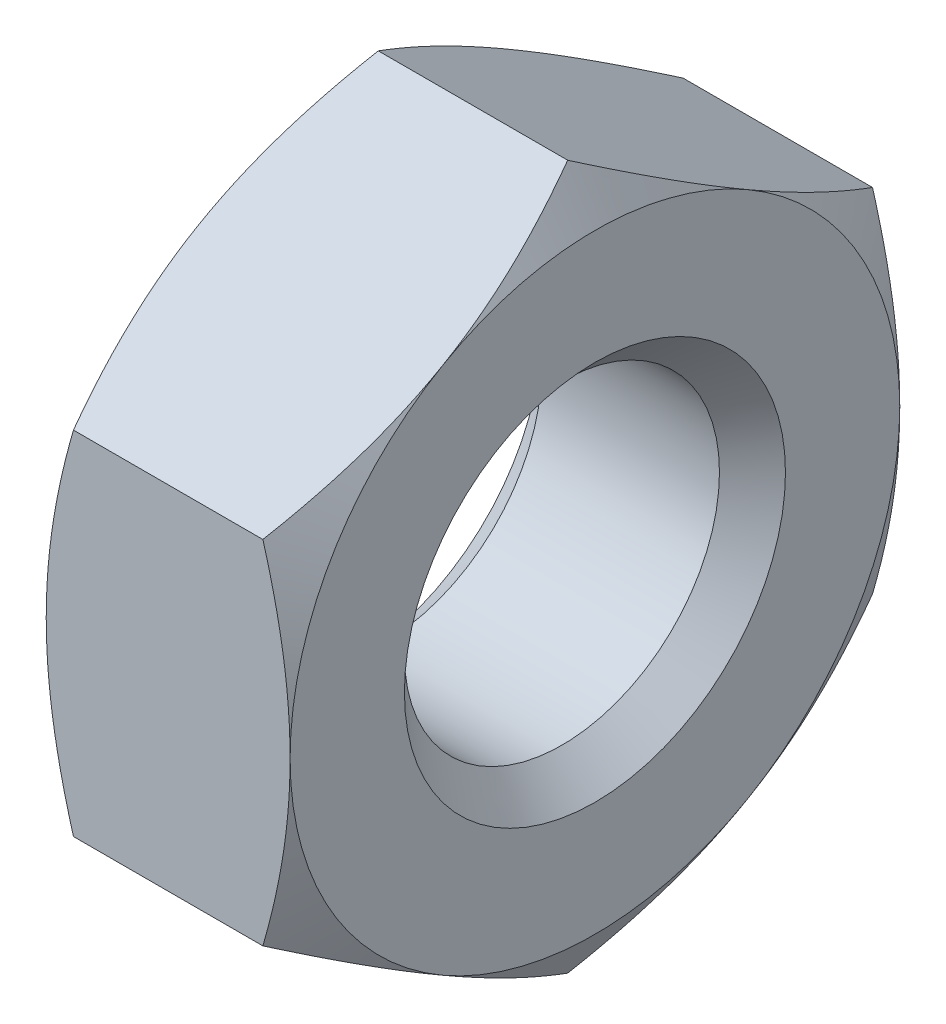
SolidWorks part; units mm, degrees
ref_plane "前视基准面" through (0, 0, 0) normal (0, 0, 1) x (1, 0, 0)
ref_plane "上视基准面" through (0, 0, 0) normal (0, 1, 0) x (1, 0, 0)
ref_plane "右视基准面" through (0, 0, 0) normal (1, 0, 0) x (0, 0, -1)
sketch "草图1" plane through (0, 0, 0) normal (0, 0, 1) x (1, 0, 0)
  line L0 (-1.6, 0) -> (-1.6, 4)
  line L1 (-1.6, 4) -> (-1.1381, 4.8)
  line L2 (-1.1381, 4.8) -> (1.1381, 4.8)
  line L3 (1.1381, 4.8) -> (1.6, 4)
  line L4 (1.6, 4) -> (1.6, 0)
  line L5 (1.6, 0) -> (-1.6, 0)
  line L6 (1.6, 0) -> (-1.6, 0) construction
revolve "旋转1" add sketch "草图1" angle 360 about L6 reverse direction yes
sketch "草图2" plane through (0, 0, 0) normal (1, 0, 0) x (0, 0, -1)
  line L0 (-9.2, -9.2) -> (9.2, -9.2)
  line L1 (9.2, -9.2) -> (9.2, 9.2)
  line L2 (9.2, 9.2) -> (-9.2, 9.2)
  line L3 (-9.2, 9.2) -> (-9.2, -9.2)
  line L4 (-4, 2.3094) -> (-4, -2.3094)
  line L5 (-4, -2.3094) -> (0, -4.6188)
  line L6 (0, -4.6188) -> (4, -2.3094)
  line L7 (4, -2.3094) -> (4, 2.3094)
  line L8 (4, 2.3094) -> (0, 4.6188)
  line L9 (0, 4.6188) -> (-4, 2.3094)
extrude "切除-拉伸1" cut sketch "草图2" along normal blind 3.2 and the other way blind 3.2
sketch "草图3" plane through (0, 0, 0) normal (0, 0, 1) x (1, 0, 0)
  line L0 (-1.6, 0) -> (-1.6, 2.5)
  line L1 (-1.6, 2.5) -> (-1.167, 2.067)
  line L2 (-1.167, 2.067) -> (1.167, 2.067)
  line L3 (1.167, 2.067) -> (1.6, 2.5)
  line L4 (1.6, 2.5) -> (1.6, 0)
  line L5 (1.6, 0) -> (-1.6, 0)
  line L6 (1.6, 0) -> (-1.6, 0) construction
revolve "切除-旋转1" cut sketch "草图3" angle 360 about L6 reverse direction yes
cosmetic thread "装饰螺纹线1" parameters "D1"=2.767, "D2"=5
ref_plane "n_b XY" through (0, 0, 0) normal (1, 0, 0) x (0, 0, -1)
ref_plane "n_b XZ" through (0, 0, 0) normal (0, -1, 0) x (1, 0, 0)
ref_plane "n_b YZ" through (0, 0, 0) normal (0, 0, -1) x (-1, 0, 0)
ref_axis "n_b X" through (0, 0, 80.9) along (0, 0, -1)
ref_axis "n_b Y" through (0, -50, 0) along (0, 1, 0)
ref_axis "n_b Z" through (80.9, 0, 0) along (-1, 0, 0)
sketch3d "n_b"
  point P0 (0, 0, 0)
